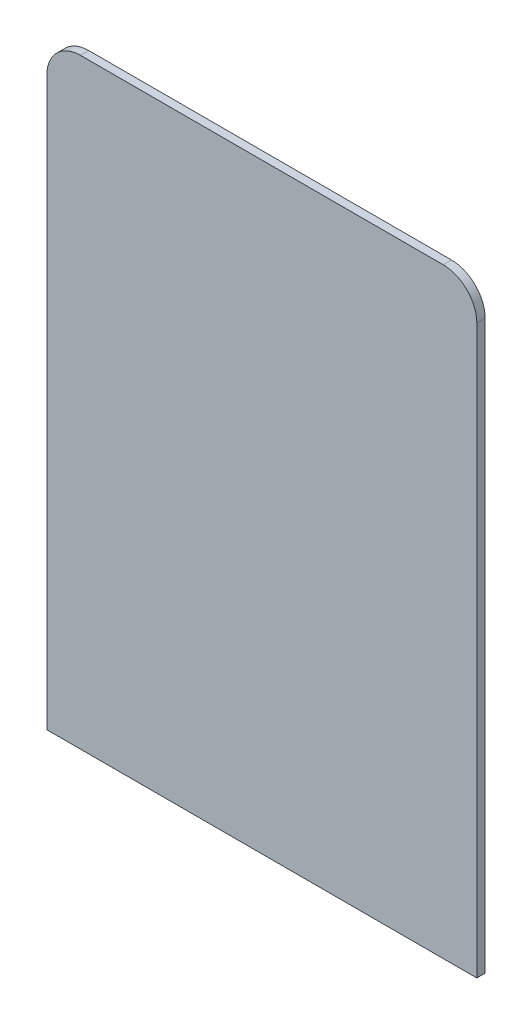
SolidWorks part; units mm, degrees
ref_plane "前视基准面" through (0, 0, 0) normal (0, 0, 1) x (1, 0, 0)
ref_plane "上视基准面" through (0, 0, 0) normal (0, 1, 0) x (1, 0, 0)
ref_plane "右视基准面" through (0, 0, 0) normal (1, 0, 0) x (0, 0, -1)
sketch "草图1" plane through (0, 0, 0) normal (0, 0, 1) x (1, 0, 0)
  line L1 (-41.75, 66.25) -> (-6.75, 66.25)
  line L2 (-45, 63) -> (-45, 8.25)
  line L3 (-45, 8.25) -> (-3.5, 8.25)
  line L4 (-3.5, 63) -> (-3.5, 8.25)
  arc A0 (-6.75, 66.25) -> (-3.5, 63) centre (-6.75, 63) cw
  arc A1 (-41.75, 66.25) -> (-45, 63) centre (-41.75, 63) ccw
  point P7 (-3.5, 66.25)
  point P10 (-45, 66.25)
  dimension "D3" = 3.25
  dimension "D4" = 3.25
  dimension "D1" = 41.5
  dimension "D2" = 58
extrude "凸台-拉伸1" add sketch "草图1" along normal blind 0.8 contours L2 L3 L4 A0 L1 A1
